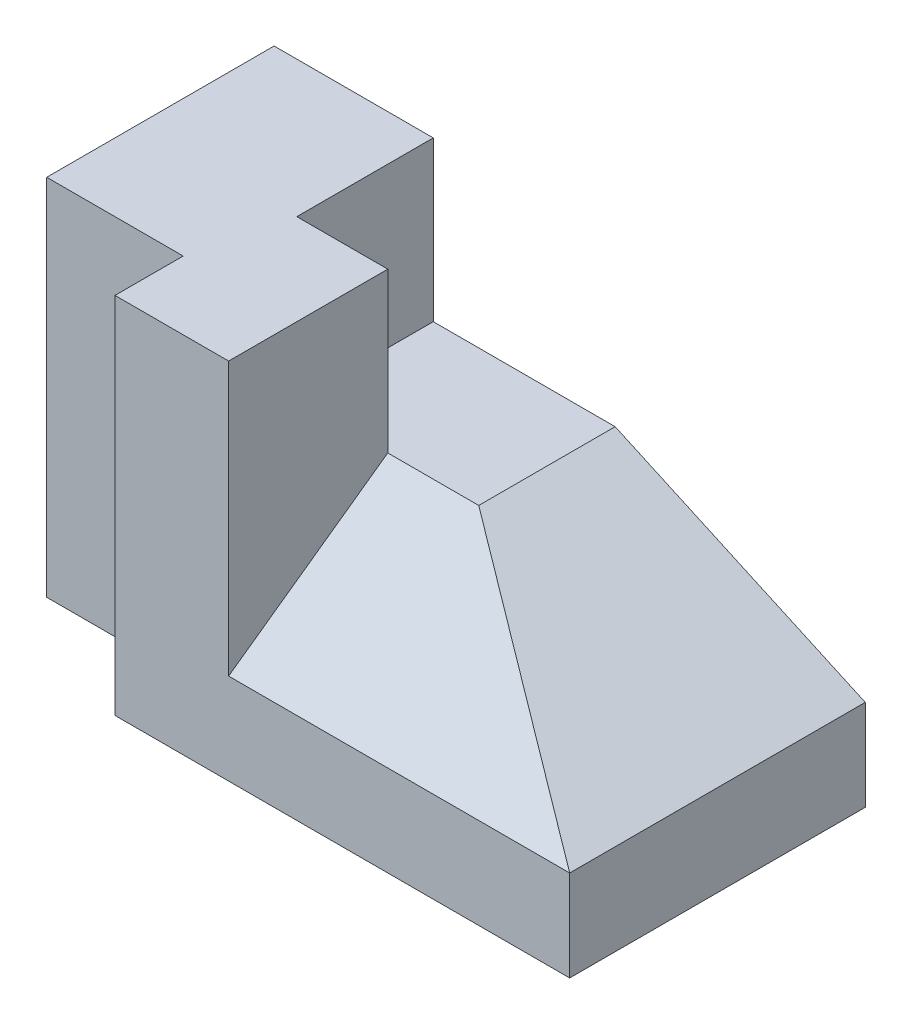
SolidWorks part; units mm, degrees
ref_plane "Front Plane" through (0, 0, 0) normal (0, 0, 1) x (1, 0, 0)
ref_plane "Top Plane" through (0, 0, 0) normal (0, 1, 0) x (1, 0, 0)
ref_plane "Right Plane" through (0, 0, 0) normal (1, 0, 0) x (0, 0, -1)
sketch "Sketch1" plane through (0, 0, 0) normal (0, 0, 1) x (1, 0, 0)
  line L0 (0, 0) -> (-30, 0)
  line L1 (-30, 0) -> (-30, 80)
  line L2 (-30, 80) -> (0, 80)
  line L3 (0, 80) -> (0, 0)
  line L4 (0, 80) -> (25, 80)
  line L5 (25, 80) -> (25, 20)
  line L6 (25, 20) -> (100, 20)
  line L7 (100, 20) -> (100, 0)
  line L8 (100, 0) -> (0, 0)
  dimension "D1" = 80
  dimension "D2" = 30
  dimension "D3" = 25
  dimension "D4" = 100
  dimension "D5" = 20
extrude "Boss-Extrude1" add sketch "Sketch1" against normal blind 50 contours L3 L2 L1 L0 region at (-15, 40, 0)
extrude "Boss-Extrude2" add sketch "Sketch1<3>" along normal blind 15 separate body contours L8 L7 L6 L5 L4 L3 region at (1.2806, 40, 0)
sketch "Sketch1<3>" plane through (0, 0, 0) normal (0, 0, 1) x (1, 0, 0) same geometry as "Sketch1"
extrude "Boss-Extrude3" add sketch "Sketch1<4>" against normal blind 20 contours L8 L7 L6 L5 L4 L3 region at (1.2806, 40, 0)
sketch "Sketch1<4>" plane through (0, 0, 0) normal (0, 0, 1) x (1, 0, 0) same geometry as "Sketch1"
sketch "Sketch2" plane through (0, 0, -20) normal (0, 0, -1) x (-1, 0, 0)
  line L0 (0, 0) -> (0, 45)
  line L1 (0, 80) -> (0, 0) construction
  line L2 (0, 45) -> (-25, 45)
  line L3 (-25, 80) -> (-25, 20) construction
  line L4 (-25, 45) -> (-25, 0)
  line L5 (-100, 0) -> (0, 0) construction
  line L6 (-25, 0) -> (0, 0)
  dimension "D1" = 45
extrude "Boss-Extrude4" add sketch "Sketch2" along normal blind 30
sketch "Sketch3" plane through (0, 0, 15) normal (0, 0, 1) x (1, 0, 0)
  line L0 (25, 20) -> (25, 45)
  line L1 (25, 80) -> (25, 20) construction
  line L2 (25, 20) -> (100, 20)
  line L3 (100, 20) -> (100, 45)
  line L4 (100, 45) -> (25, 45)
  dimension "D1" = 25
extrude "Boss-Extrude7" add sketch "Sketch3" against normal blind 65
sketch "Sketch7" plane through (0, 0, -20) normal (0, 0, -1) x (-1, 0, 0)
  line L0 (-100, 20) -> (-100, 0)
  line L1 (-100, 0) -> (-25, 0)
  line L2 (-25, 0) -> (-25, 20)
  line L3 (-25, 20) -> (-100, 20)
extrude "Boss-Extrude8" add sketch "Sketch7" along normal blind 30
sketch "Sketch8" plane through (0, 0, 15) normal (0, 0, 1) x (1, 0, 0)
  line L0 (100, 45) -> (100, 20)
  line L1 (100, 45) -> (100, 0) construction
  line L2 (100, 20) -> (45, 45)
  line L3 (100, 45) -> (25, 45) construction
  line L4 (45, 45) -> (100, 45)
  dimension "D1" = 25
  dimension "D2" = 55
extrude "Cut-Extrude6" cut sketch "Sketch8" against normal through all
sketch "Sketch9" plane through (100, 0, 0) normal (1, 0, 0) x (0, 0, -1)
  line L0 (-15, 45) -> (20, 45)
  line L1 (-15, 45) -> (-15, 20) construction
  line L2 (20, 45) -> (-15, 20)
  line L3 (-15, 20) -> (-15, 0) construction
  line L4 (-15, 20) -> (-15, 45)
  dimension "D1" = 20
  dimension "D2" = 25
  dimension "D3" = 35
extrude "Cut-Extrude7" cut sketch "Sketch9" against normal blind 75
sketch "Sketch11" plane through (0, 0, -20) normal (0, 0, -1) x (-1, 0, 0)
  line L0 (0, 80) -> (0, 45)
  line L1 (0, 45) -> (-5, 45)
  line L2 (0, 45) -> (-45, 45) construction
  line L3 (-5, 45) -> (-5, 80)
  line L4 (0, 80) -> (-25, 80) construction
  line L5 (-5, 80) -> (0, 80)
  dimension "D1" = 5
extrude "Boss-Extrude9" add sketch "Sketch11" along normal blind 30
